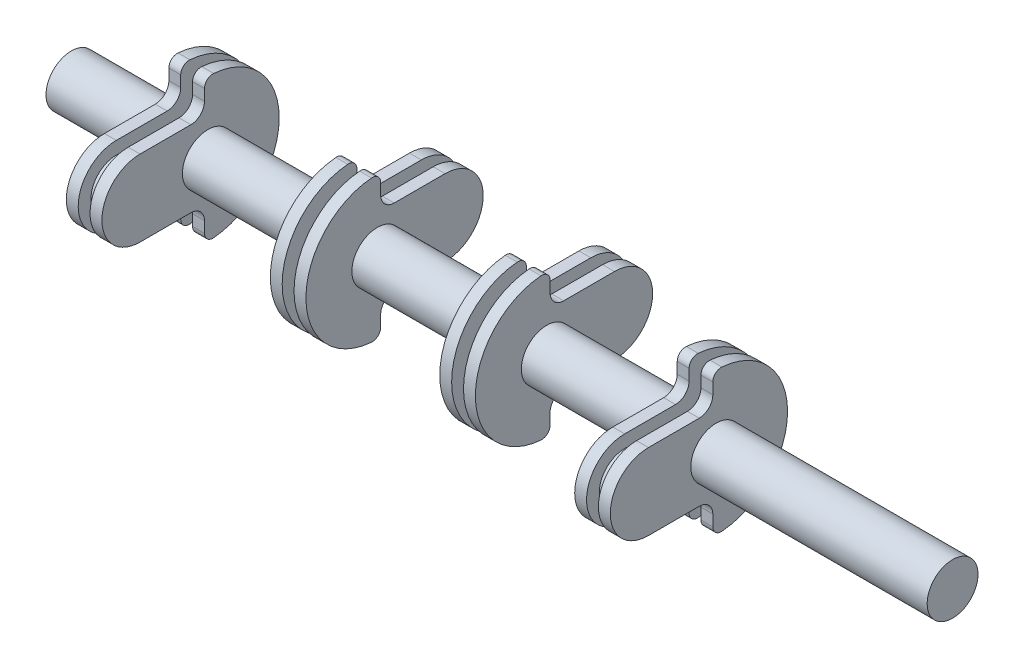
SolidWorks part; units mm, degrees
ref_plane "Front Plane" through (0, 0, 0) normal (0, 0, 1) x (1, 0, 0)
ref_plane "Top Plane" through (0, 0, 0) normal (0, 1, 0) x (1, 0, 0)
ref_plane "Right Plane" through (0, 0, 0) normal (1, 0, 0) x (0, 0, -1)
sketch "Sketch1" plane through (0, 0, 0) normal (1, 0, 0) x (0, 0, -1)
  circle A0 centre (0, 0) radius 15
  dimension "D1" = 30
extrude "Boss-Extrude1" add sketch "Sketch1" along normal blind 400
sketch "Sketch2" plane through (400, 0, 0) normal (-1, 0, 0) x (0, 0, 1)
  line L0 (2, 30.5) -> (2, 37)
  line L1 (2, -30.5) -> (2, -37)
  line L2 (40, 22.5) -> (10, 22.5)
  line L3 (40, -22.5) -> (10, -22.5)
  circle A0 centre (40, 0) radius 15
  arc A1 (40, -22.5) -> (40, 22.5) centre (40, 0) ccw
  arc A2 (-3.4041, 41.9836) -> (-3.4041, -41.9836) centre (0, 0) ccw
  arc A4 (10, -22.5) -> (2, -30.5) centre (10, -30.5) ccw
  arc A5 (10, 22.5) -> (2, 30.5) centre (10, 30.5) cw
  arc A6 (2, -37) -> (-3.4041, -41.9836) centre (-3, -37) cw
  arc A7 (2, 37) -> (-3.4041, 41.9836) centre (-3, 37) ccw
  point P12 (0, 0)
  point P16 (-4.4338, -36.2617)
  point P19 (0, 0)
  point P21 (0, 0)
  point P22 (0, 0)
  point P23 (22.5, 0)
  point P24 (-2.5, 14.7902)
  point P25 (0, 0)
  point P26 (22.5, 0)
  point P27 (22.5, 0)
  point P28 (22.5028, 0)
  point P29 (22.2514, 0)
  point P30 (24.5632, 0)
  point P31 (0, 0)
  point P32 (0, 0)
  dimension "D2" = 30
  dimension "D3" = 22.5
  dimension "D4" = 8
  dimension "D5" = 5
  dimension "D6" = 40
  dimension "D7" = 6.5
  dimension "D8" = 6.5
  dimension "D12" = 30
extrude "Boss-Extrude2" add sketch "Sketch2" along normal blind 7 from offset 53.5 contours A1 L2 A5 L0 A7 A2 A6 L1 A4 L3
extrude "Boss-Extrude3" add sketch "Sketch2<3>" along normal blind 7 from offset 39.5 contours A1 L2 A5 L0 A7 A2 A6 L1 A4 L3
sketch "Sketch2<3>" plane through (400, 0, 0) normal (-1, 0, 0) x (0, 0, 1) same geometry as "Sketch2"
extrude "Boss-Extrude4" add sketch "Sketch2<5>" along normal blind 7 from offset 339.5 contours A1 L2 A5 L0 A7 A2 A6 L1 A4 L3
sketch "Sketch2<5>" plane through (400, 0, 0) normal (-1, 0, 0) x (0, 0, 1) same geometry as "Sketch2"
extrude "Boss-Extrude5" add sketch "Sketch2<6>" along normal blind 7 from offset 353.5 contours A1 L2 A5 L0 A7 A2 A6 L1 A4 L3
sketch "Sketch2<6>" plane through (400, 0, 0) normal (-1, 0, 0) x (0, 0, 1) same geometry as "Sketch2"
sketch "Sketch5" plane through (0, 0, 0) normal (0, 1, 0) x (1, 0, 0)
  line L0 (346.5, 19.9343) -> (346.5, -15)
  line L1 (346.5, 19.9343) -> (353.5, 19.9343)
  line L2 (346.5, -15) -> (353.5, -15)
  line L3 (353.5, 19.9343) -> (353.5, -15)
  line L4 (46.5, 17.1809) -> (46.5, -15)
  line L5 (46.5, 17.1809) -> (53.5, 17.1809)
  line L6 (46.5, -15) -> (53.5, -15)
  line L7 (53.5, 17.1809) -> (53.5, -15)
extrude "Cut-Extrude1" cut sketch "Sketch5" against normal blind 31 and the other way blind 60
extrude "Boss-Extrude6" add sketch "Sketch2<8>" along normal blind 7 from offset 46.5 contours A0
sketch "Sketch2<8>" plane through (400, 0, 0) normal (-1, 0, 0) x (0, 0, 1) same geometry as "Sketch2"
extrude "Boss-Extrude7" add sketch "Sketch2<9>" along normal blind 7 from offset 346.5 contours A0
sketch "Sketch2<9>" plane through (400, 0, 0) normal (-1, 0, 0) x (0, 0, 1) same geometry as "Sketch2"
sketch "Sketch6" plane through (0, 0, 0) normal (1, 0, 0) x (0, 0, -1)
  line L0 (2, 30.5) -> (2, 37)
  line L1 (2, -30.5) -> (2, -37)
  line L2 (40, 22.5) -> (10, 22.5)
  line L3 (-40, 22.5) -> (-10, 22.5) construction
  line L4 (40, -22.5) -> (10, -22.5)
  circle A0 centre (40, 0) radius 15
  arc A2 (40, -22.5) -> (40, 22.5) centre (40, 0) ccw
  arc A3 (-3.4041, 41.9836) -> (-3.4041, -41.9836) centre (0, 0) ccw
  arc A6 (2, -37) -> (-3.4041, -41.9836) centre (-3, -37) cw
  arc A7 (2, 37) -> (-3.4041, 41.9836) centre (-3, 37) ccw
  arc A8 (10, 22.5) -> (2, 30.5) centre (10, 30.5) cw
  arc A9 (10, -22.5) -> (2, -30.5) centre (10, -30.5) ccw
  point P6 (2, -42.0739)
  point P11 (2, 27.8605)
  point P20 (-9.0101, 22.5)
  point P23 (0, 0)
  point P24 (0, 0)
  point P25 (0, 0)
  dimension "D1" = 30
  dimension "D3" = 45
  dimension "D4" = 5
  dimension "D5" = 8
  dimension "D2" = 40
  dimension "D6" = 30
  dimension "D7" = 6.5
extrude "Boss-Extrude8" add sketch "Sketch6" along normal blind 7 from offset 139.5 contours A3 A6 L1 A9 L4 A2 L2 A8 L0 A7
extrude "Boss-Extrude9" add sketch "Sketch6<3>" along normal blind 7 from offset 153.5 contours A2 L2 A8 L0 A7 A3 A6 L1 A9 L4
sketch "Sketch6<3>" plane through (0, 0, 0) normal (1, 0, 0) x (0, 0, -1) same geometry as "Sketch6"
extrude "Boss-Extrude10" add sketch "Sketch6<4>" along normal blind 7 from offset 239.5 contours A2 L2 A8 L0 A7 A3 A6 L1 A9 L4
sketch "Sketch6<4>" plane through (0, 0, 0) normal (1, 0, 0) x (0, 0, -1) same geometry as "Sketch6"
extrude "Boss-Extrude11" add sketch "Sketch6<5>" along normal blind 7 from offset 253.5 contours A2 L2 A8 L0 A7 A3 A6 L1 A9 L4
sketch "Sketch6<5>" plane through (0, 0, 0) normal (1, 0, 0) x (0, 0, -1) same geometry as "Sketch6"
sketch "Sketch8" plane through (0, 0, 0) normal (0, 1, 0) x (1, 0, 0)
  line L1 (146.5, 15) -> (153.5, 15)
  line L2 (146.5, 15) -> (146.5, -15)
  line L3 (146.5, -15) -> (153.5, -15)
  line L4 (153.5, 15) -> (153.5, -15)
  line L5 (246.5, 15) -> (253.5, 15)
  line L6 (246.5, 15) -> (246.5, -15)
  line L7 (246.5, -15) -> (253.5, -15)
  line L8 (253.5, 15) -> (253.5, -15)
extrude "Cut-Extrude3" cut sketch "Sketch8" against normal blind 33 and the other way blind 33
extrude "Boss-Extrude12" add sketch "Sketch6<6>" along normal blind 7 from offset 146.5 contours A0
sketch "Sketch6<6>" plane through (0, 0, 0) normal (1, 0, 0) x (0, 0, -1) same geometry as "Sketch6"
extrude "Boss-Extrude13" add sketch "Sketch6<7>" along normal blind 7 from offset 246.5 contours A0
sketch "Sketch6<7>" plane through (0, 0, 0) normal (1, 0, 0) x (0, 0, -1) same geometry as "Sketch6"
sketch "Sketch9" plane through (400, 0, 0) normal (1, 0, 0) x (0, 0, -1)
  circle A0 centre (0, 0) radius 15
extrude "Boss-Extrude14" add sketch "Sketch9" along normal blind 100
sketch "Sketch10" plane through (0, 0, 0) normal (-1, 0, 0) x (0, 0, 1)
  circle A0 centre (0, 0) radius 15
extrude "Boss-Extrude15" add sketch "Sketch10" along normal blind 20
